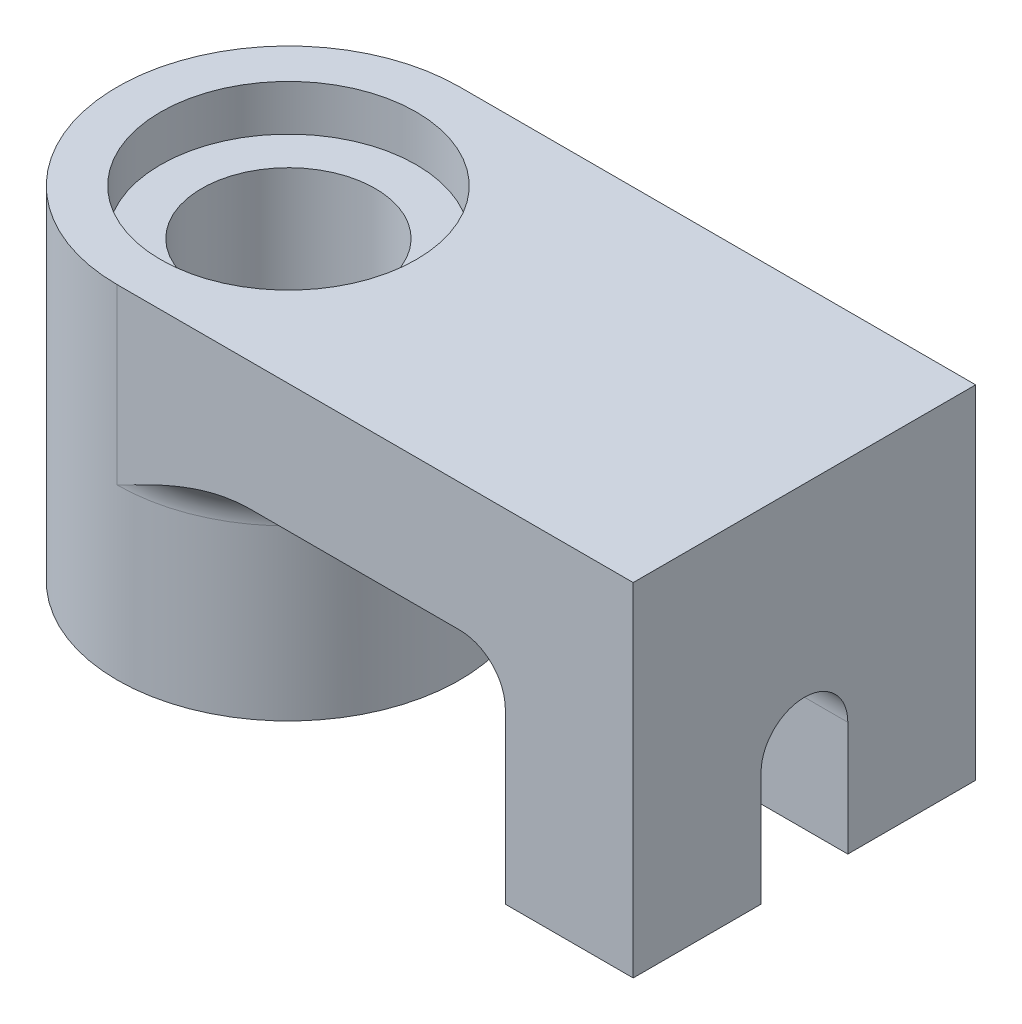
SolidWorks part; units mm, degrees
ref_plane "Front Plane" through (0, 0, 0) normal (0, 0, 1) x (1, 0, 0)
ref_plane "Top Plane" through (0, 0, 0) normal (0, 1, 0) x (1, 0, 0)
ref_plane "Right Plane" through (0, 0, 0) normal (1, 0, 0) x (0, 0, -1)
sketch "Sketch1" plane through (0, 0, 0) normal (0, 1, 0) x (1, 0, 0)
  line L0 (-19, 0) -> (19, 0) construction
  circle A0 centre (0, 0) radius 37.5
  dimension "D1" = 75
extrude "Boss-Extrude2" add sketch "Sketch1" along normal blind 75
sketch "Sketch2" plane through (0, 75, 0) normal (0, 1, 0) x (1, 0, 0)
  line L0 (0, 37.5) -> (0, -37.5) construction
  line L1 (0, 37.5) -> (113, 37.5)
  line L2 (113, 37.5) -> (113, -37.5)
  line L3 (113, -37.5) -> (0, -37.5)
  circle A0 centre (0, 0) radius 37.5 construction
  arc A1 (0, -37.5) -> (0, 37.5) centre (0, 0) ccw
  dimension "D1" = 113
extrude "Boss-Extrude6" add sketch "Sketch2" against normal blind 28
sketch "Sketch4" plane through (113, 0, 0) normal (1, 0, 0) x (0, 0, -1)
  line L0 (37.5, 47) -> (37.5, 75) construction
  line L1 (-37.5, 47) -> (37.5, 47) construction
  line L2 (37.5, 75) -> (-37.5, 75) construction
  line L3 (-37.5, 47) -> (-37.5, 75) construction
  line L4 (37.5, 47) -> (37.5, 75)
  line L5 (-37.5, 47) -> (37.5, 47)
  line L6 (37.5, 75) -> (-37.5, 75)
  line L7 (-37.5, 47) -> (-37.5, 75)
  line L8 (-37.5, 47) -> (-37.5, 0)
  line L9 (-37.5, 47) -> (-37.5, 0) construction
  line L10 (-37.5, 0) -> (37.5, 0)
  line L13 (37.5, 47) -> (37.5, 0)
  line M4 (-37.5, 47) -> (37.5, 47)
extrude "Boss-Extrude7" add sketch "Sketch4" against normal blind 28 contours L13 L8 L10 M4 region at (113, 23.5, 0)
sketch "Sketch5" plane through (113, 0, 0) normal (1, 0, 0) x (0, 0, -1)
  line L0 (0, 0) -> (0, 75) construction
  line L1 (37.5, 75) -> (-37.5, 75) construction
  line L2 (9.5, 0) -> (-9.5, 0)
  line L3 (-37.5, 0) -> (37.5, 0) construction
  line L4 (-9.5, 0) -> (-9.5, 25)
  line L5 (9.5, 0) -> (9.5, 25)
  arc A0 (-9.5, 25) -> (9.5, 25) centre (0, 25) cw
  dimension "D1" = 9.5
  dimension "D2" = 25
extrude "Cut-Extrude1" cut sketch "Sketch5" against normal blind 28
fillet "Fillet1" radius 10 2 edges at (37.5, 47, 0) (85, 47, 0)
sketch "Sketch6" plane through (0, 0, 0) normal (0, -1, 0) x (1, 0, 0)
  line L0 (0, 37.5) -> (0, -37.5) construction
  circle A0 centre (0, 0) radius 28
  dimension "D1" = 56
ref_plane "Plane1" through (0, 37.5, 0) normal (0, -1, 0) x (-1, 0, 0)
extrude "Cut-Extrude2" cut sketch "Sketch6" against normal blind 10 contours A0
sketch "Sketch8" plane through (0, 75, 0) normal (0, 1, 0) x (1, 0, 0)
  line L0 (0, 37.5) -> (0, -37.5) construction
  circle A0 centre (0, 0) radius 28
  dimension "D1" = 56
extrude "Cut-Extrude3" cut sketch "Sketch8" against normal blind 10
sketch "Sketch9" plane through (0, 10, 0) normal (0, -1, 0) x (1, 0, 0)
  line L0 (-19, 0) -> (20.0165, 0) construction
  line L2 (18.3303, 5) -> (22, 5)
  line L4 (18.3303, -5) -> (22, -5)
  line L5 (22, 5) -> (22, -5)
  arc A0 (18.3303, 5) -> (18.3303, -5) centre (0, 0) ccw
  point P1 (22, 0)
  dimension "D2" = 41
  dimension "D3" = 19
  dimension "D1" = 10
extrude "Cut-Extrude4" cut sketch "Sketch9" against normal blind 55
